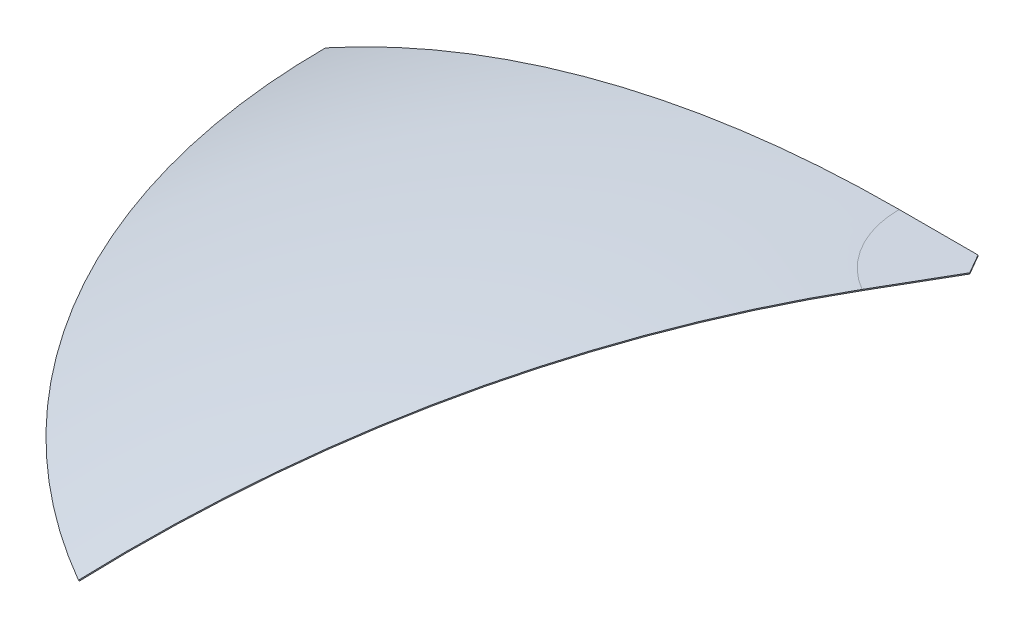
SolidWorks part; units mm, degrees
ref_plane "Front Plane" through (0, 0, 0) normal (0, 0, 1) x (1, 0, 0)
ref_plane "Top Plane" through (0, 0, 0) normal (0, 1, 0) x (1, 0, 0)
ref_plane "Right Plane" through (0, 0, 0) normal (1, 0, 0) x (0, 0, -1)
sketch "Sketch1" plane through (0, 0, 0) normal (0, 0, 1) x (1, 0, 0)
  line L0 (45, 1.5) -> (-45, 1.5) construction
  line L1 (45, 1.5) -> (-45, 1.5) construction
  line L2 (10, 1.5) -> (-10, 1.5) construction
  line L3 (10, 1.5) -> (-10, 1.5) construction
  line L4 (-45, 1.5) -> (-10, 1.5)
  line L6 (-45, 2) -> (-10, 2)
  line L7 (-10, 2) -> (-10, 1.5)
  line L8 (-299.7402, -63.211) -> (-299.5, -63.6495)
  line L9 (0, -998.5) -> (0, 49001.5) construction
  arc A0 (-46.0019, 1.4991) -> (-299.5, -63.6495) centre (-45, -528.1639) ccw construction
  arc A1 (-46.0019, 1.4991) -> (-299.5, -63.6495) centre (-45, -528.1639) ccw
  arc A2 (-45, 1.5) -> (-46.0019, 1.4991) centre (-45, -528.1639) ccw
  arc A3 (-46.0028, 1.9991) -> (-299.7402, -63.211) centre (-45, -528.1639) ccw
  arc A4 (-45, 2) -> (-46.0028, 1.9991) centre (-45, -528.1639) ccw
  point P17 (0, 1.5)
  dimension "D1" = 0.5
revolve "Revolve1" add sketch "Sketch1" angle 60 about L9
sketch "Sketch3" plane through (0, 2, 0) normal (0, 1, 0) x (1, 0, 0)
  line L0 (-10, 0) -> (-5, -8.6603)
  arc A0 (-10, 0) -> (-5, -8.6603) centre (0, 0) ccw construction
  arc A1 (-10, 0) -> (-5, -8.6603) centre (0, 0) ccw
  point P4 (0, 0)
extrude "Boss-Extrude1" add sketch "Sketch3" against normal up to surface (0.5 mm away) up to face at (-22.2203, 1.5, 12.8289)
